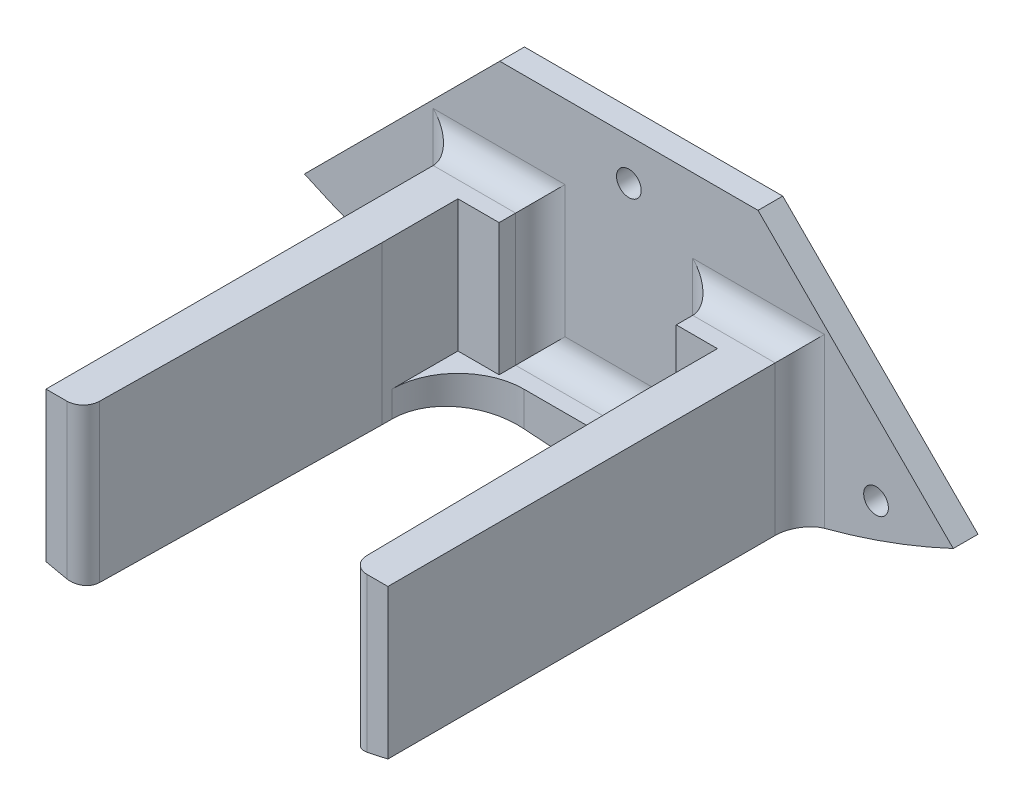
SolidWorks part; units mm, degrees
ref_plane "Alzado" through (0, 0, 0) normal (0, 0, 1) x (1, 0, 0)
ref_plane "Planta" through (0, 0, 0) normal (0, 1, 0) x (1, 0, 0)
ref_plane "Vista lateral" through (0, 0, 0) normal (1, 0, 0) x (0, 0, -1)
sketch "Croquis1" plane through (0, 0, 0) normal (0, 0, 1) x (1, 0, 0)
  line L0 (15.6764, -60) -> (-15.6764, -60)
  line L1 (-15.6764, -60) -> (-39.3766, -83.7002)
  line L2 (15.6764, -60) -> (39.3766, -83.7002)
  circle A3 centre (-30, -83.3725) radius 1.5
  circle A4 centre (30, -83.3725) radius 1.5
  circle A5 centre (0, -65) radius 1.5
  circle A6 centre (0, 0) radius 88.6057 construction
  arc A7 (-39.3766, -83.7002) -> (39.3766, -83.7002) centre (0, 0) ccw
  point P13 (0, -60)
  dimension "D4" = 177.2115
  dimension "D5" = 3
  dimension "D9" = 185
  dimension "D1" = 65
  dimension "D2" = 30
  dimension "D3" = 30
  dimension "D6" = 5
  dimension "D7" = 45
  dimension "D8" = 45
extrude "Saliente-Extruir1" add sketch "Croquis1" along normal blind 3
sketch "Croquis2" plane through (0, 0, 3) normal (0, 0, 1) x (1, 0, 0)
  line L0 (-15.75, -80) -> (15.75, -80) construction
  line L1 (0, -72) -> (0, -88) construction
  line L2 (-15.75, -80) -> (-15.75, -72)
  line L3 (-15.75, -72) -> (-10.75, -72)
  line L4 (-10.75, -72) -> (-10.75, -88)
  line L5 (-10.75, -88) -> (-15.75, -88)
  line L6 (-15.75, -88) -> (-15.75, -80)
  line L7 (15.75, -80) -> (15.75, -88)
  line L8 (15.75, -88) -> (10.75, -88)
  line L9 (10.75, -88) -> (10.75, -72)
  line L10 (10.75, -72) -> (15.75, -72)
  line L11 (15.75, -72) -> (15.75, -80)
  point P3 (0, -80)
  point P8 (0, -80)
  dimension "D1" = 31.5
  dimension "D2" = 16
  dimension "D3" = 80
  dimension "D4" = 5
  dimension "D5" = 5
extrude "Saliente-Extruir2" add sketch "Croquis2" along normal blind 5
sketch "Croquis4" plane through (0, -88, 0) normal (0, -1, 0) x (1, 0, 0)
  line L0 (-15.75, 3) -> (-20.75, 3)
  line L1 (39.3766, 3) -> (-39.3766, 3) construction
  line L2 (-20.75, 3) -> (-20.75, 53)
  line L3 (-20.75, 53) -> (-15.75, 53)
  line L4 (-15.75, 53) -> (-15.75, 16)
  line L5 (-7.75, 8) -> (7.75, 8)
  line L6 (15.75, 16) -> (15.75, 53)
  line L7 (15.75, 53) -> (20.75, 53)
  line L8 (20.75, 53) -> (20.75, 3)
  line L9 (20.75, 3) -> (-15.75, 3)
  arc A0 (7.75, 8) -> (15.75, 16) centre (7.75, 16) ccw
  arc A1 (-15.75, 16) -> (-7.75, 8) centre (-7.75, 16) ccw
  point P17 (15.75, 8)
  point P20 (-15.75, 8)
  dimension "D5" = 8
  dimension "D1" = 50
  dimension "D2" = 50
  dimension "D3" = 5
  dimension "D4" = 5
extrude "Saliente-Extruir3" add sketch "Croquis4" along normal up to surface (2.1426 mm away) up to face at (0, -88.1001, 1.5)
sketch "Croquis5" plane through (0, -88, 0) normal (0, 1, 0) x (1, 0, 0)
  line L0 (-15.75, -3) -> (-15.75, -53)
  line L1 (-15.75, -53) -> (-20.75, -53)
  line L2 (-20.75, -53) -> (-20.75, -3)
  line L3 (-20.75, -3) -> (-15.75, -3)
  line L4 (15.75, -3) -> (20.75, -3)
  line L5 (20.75, -3) -> (20.75, -53)
  line L6 (20.75, -53) -> (15.75, -53)
  line L7 (15.75, -53) -> (15.75, -3)
extrude "Saliente-Extruir4" add sketch "Croquis5" along normal up to surface (16 mm away) up to face at (13.25, -72, 5.5)
chamfer "Chaflán1" distance 0.5 angle 89.2 2 edges at (15.75, -81.5746, 53) (-15.75, -81.5746, 53) first distance on face at (18.2517, -81.3316, 53) first distance on face at (-18.2517, -81.3316, 53)
fillet "Redondeo1" radius 2 2 edges at (16.25, -81.5307, 53) (-16.25, -81.5307, 53)
fillet "Redondeo2" radius 3 7 edges at (-15.75, -72, 3) (-10.75, -80, 3) (0, -88, 3) (10.75, -80, 3) (15.75, -72, 3) (-20.75, -81.0713, 3) (20.75, -81.0713, 3)
